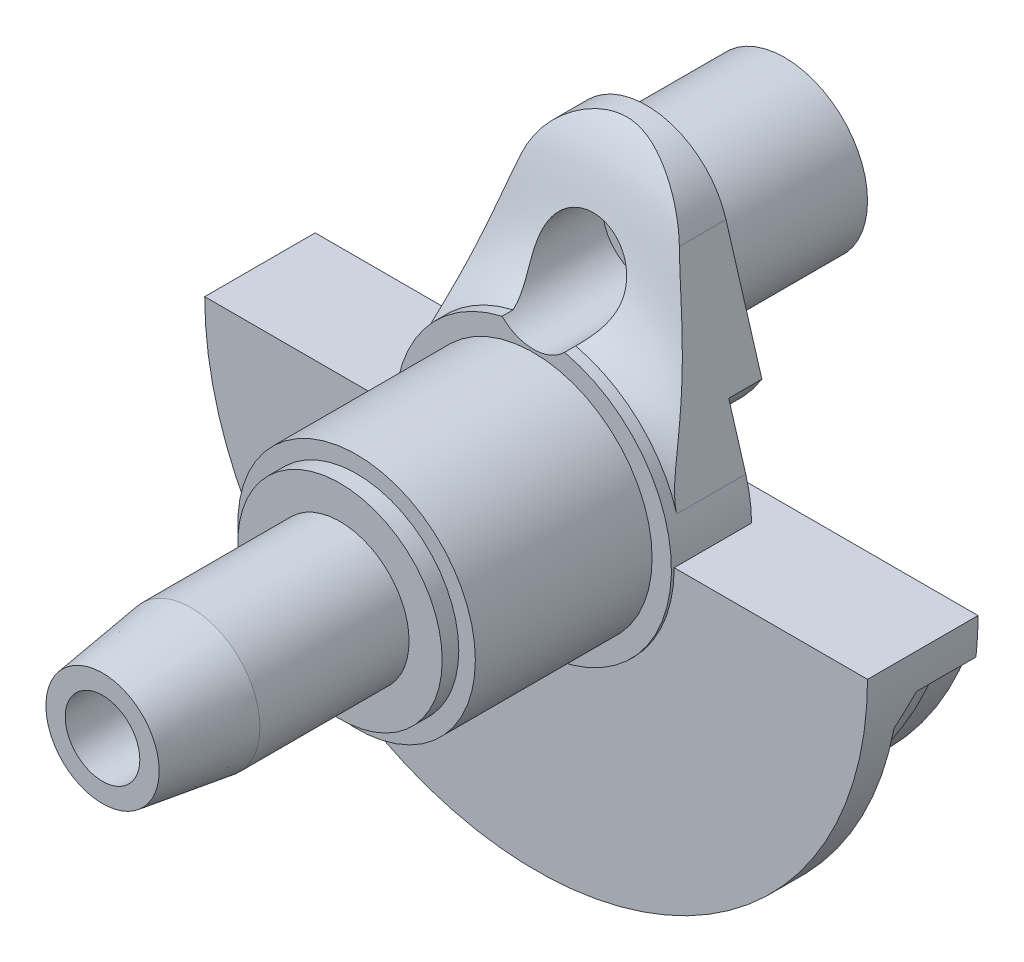
SolidWorks part; units mm, degrees
ref_plane "Front Plane" through (0, 0, 0) normal (0, 0, 1) x (1, 0, 0)
ref_plane "Top Plane" through (0, 0, 0) normal (0, 1, 0) x (1, 0, 0)
ref_plane "Right Plane" through (0, 0, 0) normal (1, 0, 0) x (0, 0, -1)
sketch "Sketch1" plane through (0, 0, 0) normal (0, 0, 1) x (1, 0, 0)
  line L0 (0, 0) -> (0, 70) construction
  line L1 (-28.7494, 78.5714) -> (-47.9157, 14.2857)
  line L2 (28.7494, 78.5714) -> (47.9157, 14.2857)
  line L3 (-41.7399, 35) -> (41.7399, 35) construction
  line L4 (-120, 0) -> (-50, 0)
  line L5 (120, 0) -> (50, 0)
  circle A0 centre (0, 0) radius 50
  arc A1 (-28.7494, 78.5714) -> (28.7494, 78.5714) centre (0, 70) cw
  arc A2 (120, 0) -> (-120, 0) centre (0, 0) cw
  point P10 (0, 35)
  dimension "D1" = 100
  dimension "D2" = 30
  dimension "D4" = 120
  dimension "D3" = 70
extrude "Boss-Extrude1" add sketch "Sketch1" along normal blind 1 and the other way blind 40 contours A0 region at (0, 0, 0)
extrude "Boss-Extrude2" add sketch "Sketch1<3>" against normal up to surface (40 mm away) contours A2 L5 A0 L4 | A1 L1 A0 L2 region at (0, 66.8029, 0) region at (0, -57.171, 0) up to face at (50, 0, -40)
sketch "Sketch1<3>" plane through (0, 0, 0) normal (0, 0, 1) x (1, 0, 0) same geometry as "Sketch1"
sketch "Sketch2" plane through (0, 0, 0) normal (1, 0, 0) x (0, 0, -1)
  line L0 (-1, 0) -> (-1, 43)
  line L1 (-1, 50) -> (-1, -50) construction
  line L2 (-1, 43) -> (-65, 43)
  line L3 (-65, 43) -> (-65, 37)
  line L4 (-65, 37) -> (-71, 37)
  line L5 (-71, 37) -> (-71, 25)
  line L6 (-71, 25) -> (-125, 25)
  line L7 (-125, 25) -> (-125, 0)
  line L8 (-125, 0) -> (-1, 0)
  dimension "D1" = 43
  dimension "D2" = 64
  dimension "D3" = 6
  dimension "D4" = 12
  dimension "D5" = 54
revolve "Revolve1" add sketch "Sketch2" angle 360 about L8
sketch "Sketch3" plane through (0, 0, 125) normal (0, 0, 1) x (1, 0, 0)
  circle A1 centre (0, 0) radius 25
  circle A2 centre (0, 0) radius 25
  dimension "D1" = 0
extrude "Boss-Extrude3" add sketch "Sketch3" along normal blind 32 draft 8
sketch "Sketch4" plane through (0, 0, -40) normal (0, 0, -1) x (-1, 0, 0)
  circle A0 centre (0, 60) radius 30
  arc A2 (28.7494, 78.5714) -> (-28.7494, 78.5714) centre (0, 70) ccw construction
  dimension "D1" = 60
extrude "Boss-Extrude4" add sketch "Sketch4" along normal blind 50
sketch "Sketch12" plane through (0, 0, 0) normal (1, 0, 0) x (0, 0, -1)
  line L0 (-1, 50) -> (-1, 100)
  line L2 (-1, 50) -> (3, 50)
  line L4 (3, 50) -> (20, 56.1875) construction
  line L5 (20, 56.1875) -> (20, 78.5714) construction
  line L6 (20, 78.5714) -> (24, 92.9714) construction
  line L8 (24, 92.9714) -> (32.8, 100) construction
  line L9 (40, 100) -> (0, 100) construction
  line L10 (-1, 100) -> (32.8, 100)
  line L11 (40, 78.5714) -> (0, 78.5714) construction
  spline S0 degree 4 poles (3, 50) (20, 56.1875) (20, 78.5714) (24, 92.9714) (32.8, 100) knots 0 0 0 0 0 1 1 1 1 1
  dimension "D1" = 4
  dimension "D2" = 20
  dimension "D3" = 7.2
  dimension "D4" = 4
  dimension "D5" = 14.4
revolve "Cut-Revolve2" cut sketch "Sketch12" angle 180 mid plane about axis through (0, 0, -40) along (0, 0, 1)
sketch "Sketch5" plane through (0, 0, -90) normal (0, 0, -1) x (-1, 0, 0)
  circle A2 centre (0, 60) radius 21
  circle A3 centre (0, 60) radius 21
  dimension "D1" = 9
extrude "Cut-Extrude1" cut sketch "Sketch5" against normal blind 25
sketch "Sketch6" plane through (0, 0, -65) normal (0, 0, -1) x (-1, 0, 0)
  circle A2 centre (0, 60) radius 11
  circle A3 centre (0, 60) radius 11
  dimension "D1" = 10
extrude "Cut-Extrude2" cut sketch "Sketch6" against normal up to surface (66 mm away) up to face at (50, 0, 1)
sketch "Sketch7" plane through (0, 0, -40) normal (0, 0, -1) x (-1, 0, 0)
  circle A2 centre (0, 60) radius 16
  circle A3 centre (0, 60) radius 16
  dimension "D1" = 5
extrude "Cut-Extrude3" cut sketch "Sketch7" against normal up to surface (41 mm away) up to face at (0, -0.5, 1)
sketch "Sketch8" plane through (0, 0, 157) normal (0, 0, 1) x (1, 0, 0)
  circle A2 centre (0, 0) radius 13.5027
  circle A3 centre (0, 0) radius 13.5027
  dimension "D1" = 7
extrude "Cut-Extrude4" cut sketch "Sketch8" against normal blind 30
sketch "Sketch9" plane through (0, 0, 0) normal (1, 0, 0) x (0, 0, -1)
  line L0 (40, -120) -> (40, -94)
  line L1 (40, -120) -> (40, 0) construction
  line L2 (40, -94) -> (28, -94)
  line L3 (28, -94) -> (11.6457, -99)
  line L4 (11.6457, -99) -> (11.6457, -120)
  line L5 (0, -120) -> (40, -120) construction
  line L6 (11.6457, -120) -> (40, -120)
  line L7 (40, 30) -> (90, 30) construction
  line L8 (40, 30) -> (90, 30) construction
  dimension "D1" = 12
  dimension "D2" = 21
  dimension "D3" = 26
  dimension "D4" = 107
revolve "Cut-Revolve1" cut sketch "Sketch9" angle 140 mid plane about L8
sketch "Sketch10" plane through (0, 0, -40) normal (0, 0, -1) x (-1, 0, 0)
  line L0 (-28.7494, 78.5714) -> (-47.9157, 14.2857) construction
  line L1 (28.7494, 78.5714) -> (47.9157, 14.2857) construction
  line L2 (-41.7399, 35) -> (-47.9157, 14.2857)
  line L3 (41.7399, 35) -> (47.9157, 14.2857)
  line L4 (-50, 0) -> (50, 0)
  arc A0 (-41.7399, 35) -> (41.7399, 35) centre (0, 60) ccw
  circle A1 centre (0, 60) radius 30 construction
  circle A2 centre (0, 0) radius 50 construction
  arc A3 (-47.9157, 14.2857) -> (-50, 0) centre (0, 0) ccw
  arc A4 (50, 0) -> (47.9157, 14.2857) centre (0, 0) ccw
extrude "Cut-Extrude5" cut sketch "Sketch10" against normal up to vertex up to point (116.5219, -12.4105, -28)
equation "\"D2@Sketch1\"=\"D1@Sketch1\"*.3"
equation "\"D3@Sketch1\"=\"D1@Sketch1\"*.7"
equation "\"D4@Sketch1\"=\"D1@Sketch1\"*1.2"
equation "\"D1@Boss-Extrude1\"=\"D1@Sketch1\"*.01"
equation "\"D2@Boss-Extrude1\"=\"D1@Sketch1\"*.4"
